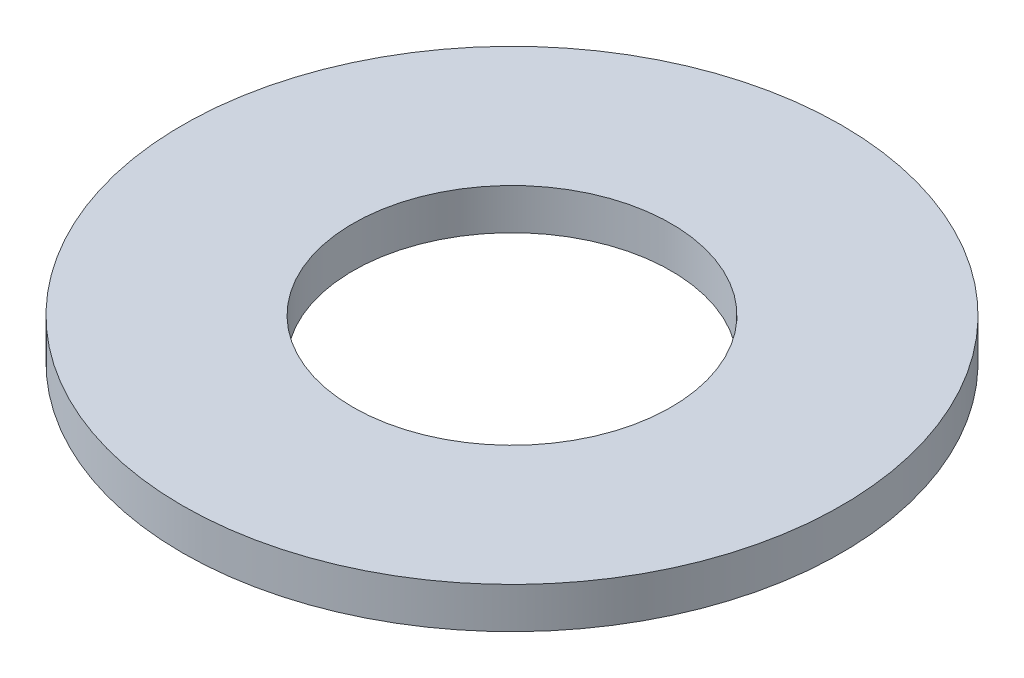
SolidWorks part; units mm, degrees
ref_plane "Front Plane" through (0, 0, 0) normal (0, 0, 1) x (1, 0, 0)
ref_plane "Top Plane" through (0, 0, 0) normal (0, 1, 0) x (1, 0, 0)
ref_plane "Right Plane" through (0, 0, 0) normal (1, 0, 0) x (0, 0, -1)
sketch "Sketch1" plane through (0, 0, 0) normal (0, 1, 0) x (1, 0, 0)
  circle A0 centre (0, 0) radius 72.5
  dimension "FLANGE_OD" = 145
extrude "Boss-Extrude1" add sketch "Sketch1" along normal blind 9
sketch "Sketch2" plane through (0, 0, 0) normal (0, 1, 0) x (1, 0, 0)
  circle A0 centre (0, 0) radius 35
  dimension "BORE_D" = 70
extrude "Cut-Extrude1" cut sketch "Sketch2" along normal through all
sketch "Sketch3" plane through (0, 9, 0) normal (0, 1, 0) x (1, 0, 0)
  circle A0 centre (0, 0) radius 29.8836 construction
  circle A1 centre (-29.8836, 0) radius 3.7274
  dimension "BOLT_D" = 7.4548
  dimension "BOLT_PCD" = 59.7671
extrude "Cut-Extrude2" cut sketch "Sketch3" against normal blind 5.4031 rebuild error yes
pattern_circular "CirPattern1" count 6 over 360 rebuild error yes
